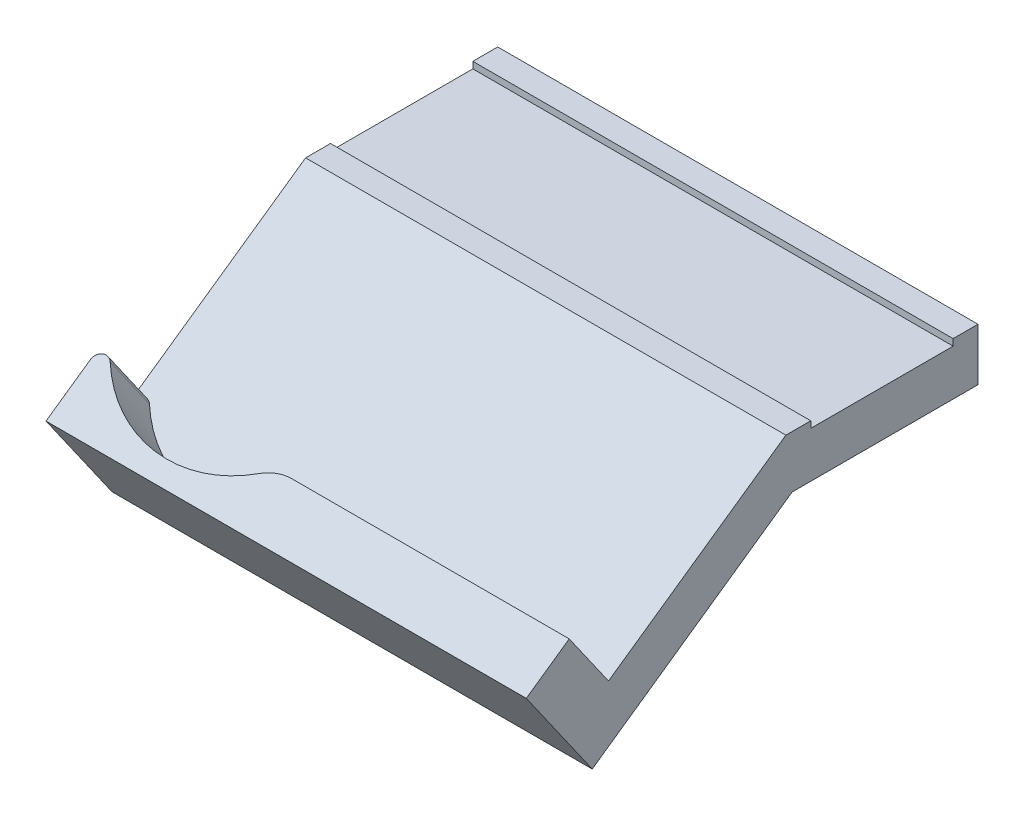
SolidWorks part; units mm, degrees
ref_plane "Front Plane" through (0, 0, 0) normal (0, 0, 1) x (1, 0, 0)
ref_plane "Top Plane" through (0, 0, 0) normal (0, 1, 0) x (1, 0, 0)
ref_plane "Right Plane" through (0, 0, 0) normal (1, 0, 0) x (0, 0, -1)
sketch "Sketch1" plane through (0, 0, 0) normal (0, 1, 0) x (1, 0, 0)
  line L1 (0, 33) -> (55, 33)
  line L2 (0, 33) -> (0, 0)
  line L3 (0, 0) -> (55, 0)
  line L4 (55, 33) -> (55, 0)
  dimension "D1" = 55
  dimension "D2" = 33
extrude "Boss-Extrude1" add sketch "Sketch1" along normal blind 50 contours L2 L3 L4 L1
sketch "Sketch4" plane through (55, 0, 0) normal (1, 0, 0) x (0, 0, -1)
  line L0 (33, 0) -> (0, 0) construction
  line L1 (-21.6788, 50.9576) -> (19.2788, 79.6364)
  line L2 (-21.6788, 50.9576) -> (7, 10)
  line L3 (7, 10) -> (47.9576, 38.6788)
  line L4 (19.2788, 79.6364) -> (47.9576, 38.6788)
  line L5 (0, 50) -> (0, 0) construction
  dimension "D1" = 50
  dimension "D2" = 50
  dimension "D3" = 10
  dimension "D4" = 7
  dimension "D5" = 35
extrude "Cut-Extrude1" cut sketch "Sketch4" against normal blind 50
sketch "Sketch5" plane through (55, 0, 0) normal (1, 0, 0) x (0, 0, -1)
  line L0 (0, 19.997) -> (0, 0) construction
  line L1 (-11.4273, 18.8824) -> (-3.2358, 24.6182)
  line L2 (-11.4273, 18.8824) -> (-5.6915, 10.6909)
  line L3 (-5.6915, 10.6909) -> (2.5, 16.4267)
  line L4 (-3.2358, 24.6182) -> (2.5, 16.4267)
  line L5 (0, 19.997) -> (7, 10) construction
  dimension "D1" = 10
  dimension "D2" = 10
  dimension "D3" = 2.5
extrude "Cut-Extrude2" cut sketch "Sketch5" against normal through all
sketch "Sketch12" plane through (55, 0, 0) normal (1, 0, 0) x (0, 0, -1)
  line L0 (2.5, 16.4267) -> (7, 10)
  line L1 (7, 10) -> (8.1878, 10.8317)
  line L2 (7, 10) -> (33, 28.2054) construction
  line L3 (8.1878, 10.8317) -> (3.6878, 17.2584)
  line L4 (3.6878, 17.2584) -> (2.5, 16.4267)
  dimension "D1" = 1.45
extrude "Boss-Extrude2" add sketch "Sketch12" against normal through all contours L3 L4 L0 L1
sketch "Sketch6" plane through (0, 3.4212, 2.3955) normal (0, 0.8192, 0.5736) x (1, 0, 0)
  line L0 (55, 8.4179) -> (0, 8.4179) construction
  line L3 (0, 55.7108) -> (0, 28.6788) construction
  circle A0 centre (12, 22.9179) radius 13.75
  dimension "D1" = 27.5
  dimension "D2" = 14.5
  dimension "D3" = 12
extrude "Cut-Extrude3" cut sketch "Sketch6" along normal through all
ref_axis "Axis2" through (12, 42.1941, 1.567) along (0, -0.8192, -0.5736)
sketch "Sketch7" plane through (55, 0, 0) normal (1, 0, 0) x (0, 0, -1)
  line L0 (0, 14.6761) -> (6.3789, 19.1427)
  line L1 (21.8766, 20.4167) -> (10.8789, 12.716) construction
  line L2 (6.3789, 19.1427) -> (10.8789, 12.716)
  line L3 (10.8789, 12.716) -> (85.0856, 64.6761)
  line L4 (85.0856, 64.6761) -> (25.4084, 64.6761)
  line L5 (25.4084, 64.6761) -> (0, 64.6761)
  line L6 (0, 64.6761) -> (0, 14.6761)
  line L7 (10.8789, 12.716) -> (0, 28.2526) construction
  line L8 (8.1878, 10.8317) -> (33, 28.2054) construction
  dimension "D1" = 50
extrude "Cut-Extrude4" cut sketch "Sketch7" against normal through all contours L5 L6 L0 L2 L3 L4
sketch "Sketch8" plane through (0, 0, 0) normal (0, 1, 0) x (1, 0, 0)
  line L0 (12, -1.567) -> (12, 11.76) construction
  line L3 (55, 33) -> (0, 33) construction
  circle A0 centre (25.75, 34.5) radius 6
  dimension "D1" = 12
  dimension "D3" = 1.5
  dimension "D2" = 13.75
extrude "Cut-Extrude5" cut sketch "Sketch8" along normal through all contours A0
sketch "Sketch9" plane through (55, 0, 0) normal (1, 0, 0) x (0, 0, -1)
  line L0 (28.5, 25.0545) -> (33, 25.0545)
  line L1 (33, 28.2054) -> (33, 0) construction
  line L2 (33, 25.0545) -> (33, 28.2054)
  line L3 (33, 28.2054) -> (28.5, 25.0545)
extrude "Cut-Extrude6" cut sketch "Sketch9" against normal through all
sketch "Sketch10" plane through (0, 0, 0) normal (0, 1, 0) x (1, 0, 0)
  line L0 (0, 28.5) -> (25.75, 28.5) construction
  line L1 (55, 28.5) -> (0, 28.5)
  line L2 (55, 28.5) -> (55, 33)
  line L3 (55, 33) -> (0, 33)
  line L4 (0, 28.5) -> (0, 33)
  line L5 (0, 28.5) -> (0, 10.8789) construction
extrude "Cut-Extrude7" cut sketch "Sketch10" along normal through all
fillet "Fillet5" radius 1 1 edges at (0, 15.9293, -8.6289) tangent propagation no
fillet "Fillet6" radius 5 1 edges at (21.4393, 14.045, -5.9378)
sketch "Sketch16" plane through (55, 0, 0) normal (1, 0, 0) x (0, 0, -1)
  line L0 (28.5, 18.5545) -> (7.554, 3.8879)
  line L1 (28.5, 25.0545) -> (28.5, 0) construction
  line L2 (7.554, 3.8879) -> (0, 14.6761)
  line L3 (0, 14.6761) -> (0, 0)
  line L4 (0, 0) -> (28.5, 0)
  line L5 (28.5, 0) -> (28.5, 18.5545)
  line L6 (8.1878, 10.8317) -> (28.5, 25.0545) construction
  line L7 (28.5, 0) -> (0, 0) construction
  dimension "D1" = 6.5
extrude "Cut-Extrude8" cut sketch "Sketch16" against normal through all
sketch "Sketch17" plane through (0, 0, -28.5) normal (0, 0, -1) x (-1, 0, 0)
  line L1 (-55, 25.0545) -> (0, 25.0545)
  line L2 (-55, 25.0545) -> (-55, 19.0545)
  line L3 (-55, 19.0545) -> (0, 19.0545)
  line L4 (0, 25.0545) -> (0, 19.0545)
  dimension "D1" = 6
extrude "Boss-Extrude4" add sketch "Sketch17" along normal blind 22
sketch "Sketch18" plane through (55, 0, 0) normal (1, 0, 0) x (0, 0, -1)
  line L0 (18.027, 11.2212) -> (37.783, 25.0545)
  line L1 (28.5, 18.5545) -> (7.554, 3.8879) construction
  line L2 (50.5, 25.0545) -> (28.5, 25.0545) construction
  line L3 (37.783, 25.0545) -> (28.5, 25.0545)
  line L4 (28.5, 25.0545) -> (14.973, 15.5828)
  line L5 (8.1878, 10.8317) -> (28.5, 25.0545) construction
  line L6 (14.973, 15.5828) -> (18.027, 11.2212)
extrude "Boss-Extrude5" add sketch "Sketch18" against normal up to surface (55 mm away) contours L0 L3 L4 L6 up to face at (0, 17.097, -24.1345)
sketch "Sketch19" plane through (0, 25.0545, 0) normal (0, 1, 0) x (1, 0, 0)
  line L0 (0, 50.5) -> (0, 28.5) construction
  line L1 (0, 47.65) -> (55, 47.65)
  line L2 (0, 47.65) -> (0, 31.35)
  line L3 (0, 31.35) -> (55, 31.35)
  line L4 (55, 47.65) -> (55, 31.35)
  line L5 (55, 50.5) -> (55, 28.5) construction
  point P8 (0, 39.5)
  dimension "D1" = 16.3
extrude "Cut-Extrude9" cut sketch "Sketch19" against normal blind 0.75
sketch "Sketch20" plane through (55, 0, 0) normal (1, 0, 0) x (0, 0, -1)
  line L0 (0, 14.6761) -> (-1.2287, 13.8158)
  line L1 (-1.2287, 13.8158) -> (6.3253, 3.0276)
  line L2 (6.3253, 3.0276) -> (7.554, 3.8879)
  line L3 (7.554, 3.8879) -> (0, 14.6761)
  line L4 (0, 14.6761) -> (3.6878, 17.2584) construction
  line L5 (29.2141, 19.0545) -> (7.554, 3.8879) construction
  dimension "D1" = 1.5
extrude "Boss-Extrude6" add sketch "Sketch20" against normal up to surface (55 mm away) contours L1 L2 L3 L0 up to face at (0, 19.4822, -28.9223)
